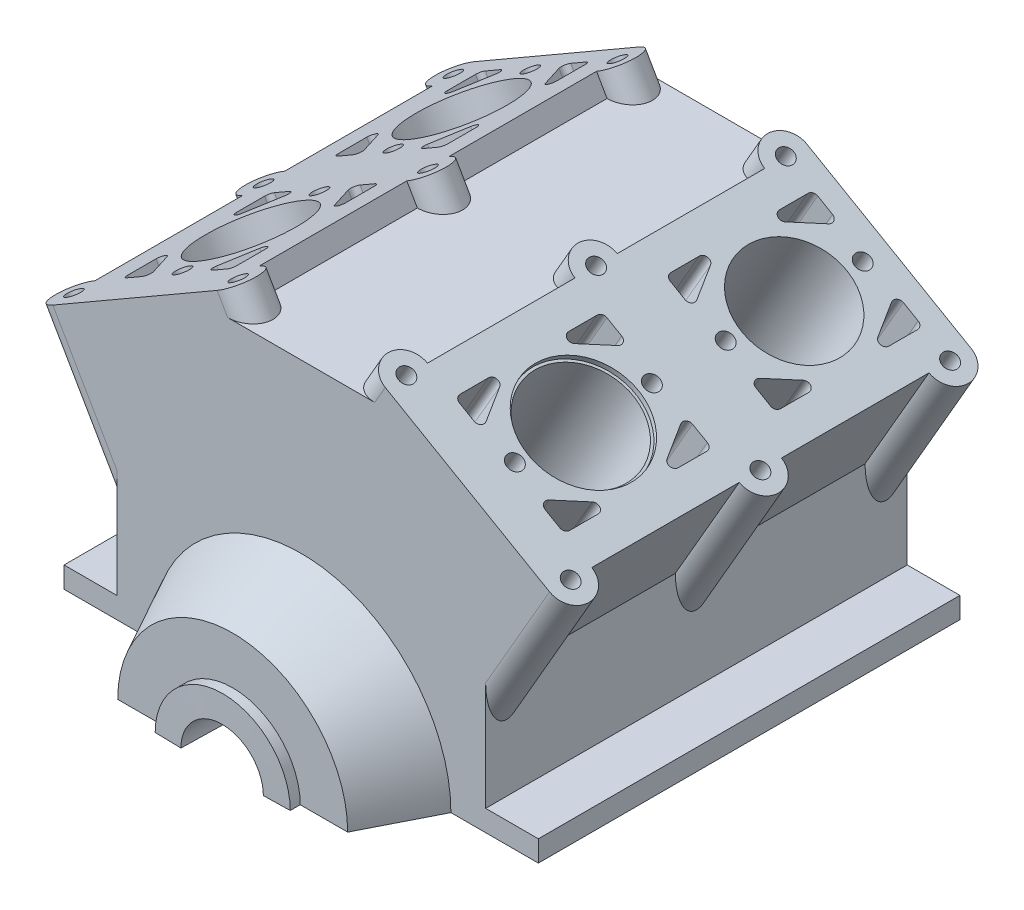
SolidWorks part; units mm, degrees
ref_plane "Front Plane" through (0, 0, 0) normal (0, 0, 1) x (1, 0, 0)
ref_plane "Top Plane" through (0, 0, 0) normal (0, 1, 0) x (1, 0, 0)
ref_plane "Right Plane" through (0, 0, 0) normal (1, 0, 0) x (0, 0, -1)
sketch "Sketch1" plane through (0, 0, 0) normal (0, 0, 1) x (1, 0, 0)
  line L0 (307.0364, 0) -> (-307.0364, 0) construction
  line L1 (0, 0) -> (0, 350) construction
  line L2 (0, 0) -> (0, 100) construction
  line L3 (-299.4563, 100) -> (299.4563, 100) construction
  line L4 (0, 0) -> (204.6694, 354.4979) construction
  line L5 (0, 0) -> (-204.6694, 354.4979) construction
  line L6 (37.5, 0) -> (225, 0)
  line L7 (225, 0) -> (225, 20)
  line L8 (225, 20) -> (175, 20)
  line L9 (175, 20) -> (175, 123.1089)
  line L10 (175, 123.1089) -> (235.6773, 228.2051)
  line L11 (235.6773, 228.2051) -> (79.7927, 318.2051)
  line L12 (79.7927, 318.2051) -> (69.7927, 300.8846)
  line L13 (69.7927, 300.8846) -> (-69.7927, 300.8846)
  line L14 (-37.5, 0) -> (-225, 0)
  line L15 (-225, 0) -> (-225, 20)
  line L16 (-225, 20) -> (-175, 20)
  line L17 (-175, 20) -> (-175, 123.1089)
  line L18 (-175, 123.1089) -> (-235.6773, 228.2051)
  line L19 (-235.6773, 228.2051) -> (-79.7927, 318.2051)
  line L20 (-79.7927, 318.2051) -> (-69.7927, 300.8846)
  arc A0 (-37.5, 0) -> (37.5, 0) centre (0, 0) cw
  point P18 (157.735, 273.2051)
  point P21 (57.735, 100)
  point P29 (0, 300.8846)
  dimension "D1" = 100
  dimension "D3" = 37.5
  dimension "D2" = 187.5
  dimension "D4" = 200
  dimension "D5" = 20
  dimension "D6" = 180
  dimension "D7" = 20
  dimension "D8" = 50
  dimension "D9" = 300.8846
extrude "Boss-Extrude1" add sketch "Sketch1" along normal blind 400
ref_plane "Plane4" through (0, 0, 380) normal (0, 0, 1) x (1, 0, 0)
sketch "Sketch2" plane through (0, 0, 380) normal (0, 0, 1) x (1, 0, 0)
  line L0 (-155, 0) -> (155, 0)
  arc A0 (-155, 0) -> (155, 0) centre (0, 0) cw
  dimension "D1" = 310
extrude "Cut-Extrude5" cut sketch "Sketch2" against normal offset from surface (360 mm away) 20 up to face at (0, 128.6442, 0)
sketch "Sketch4" plane through (157.735, 273.2051, 0) normal (0.5, 0.866, 0) x (0.866, -0.5, 0)
  line L0 (90, -400) -> (90, 0) construction
  line L1 (90, -400) -> (-90, -400) construction
  circle A0 centre (90, -380) radius 20
  dimension "D1" = 40
extrude "Head Bolt Holder" add sketch "Sketch4" against normal up to next
hole_wizard "Ø15.0 (15) Diameter Hole1" positions "3DSketch1" profile "Sketch8" hole size "Ø15.0" standard "ANSI Metric"
sketch3d "3DSketch1"
  point P0 (235.6773, 228.2051, 380)
sketch "Sketch8" plane through (235.6773, 228.2051, 380) normal (0, 0, 1) x (-0.866, 0.5, 0)
  line L0 (0, 0) -> (0, 119.5065)
  line L1 (0, 119.5065) -> (7.5, 115)
  line L2 (7.5, 115) -> (7.5, 0)
  line L5 (7.5, 0) -> (0, 0)
  line L10 (0, 119.5065) -> (-7.5, 115) construction
  line L11 (0, -6.35) -> (0, 107.95) construction
  dimension "Hole Dia." = 15
  dimension "Hole Depth" = 115
  dimension "Drill Angle" = 118
pattern_linear "LPattern4" count 3 spacing 180 along (0, 0, -1) of "Head Bolt Holder", "Ø15.0 (15) Diameter Hole1"
ref_axis "Axis1" through (0, 0, 420) along (0, 0, -1)
ref_plane "Plane9" through (0, 0, 0) normal (0.866, -0.5, 0) x (0, 0, -1)
mirror "Mirror3" about plane through (0, 0, 0) normal (0.866, -0.5, 0) of "LPattern4"
mirror "Mirror4" about plane through (0, 0, 0) normal (1, 0, 0) of "LPattern4", "Mirror3"
sketch "Sketch11" plane through (157.735, 273.2051, 0) normal (0.5, 0.866, 0) x (0.866, -0.5, 0)
  line L0 (0, -400) -> (0, -290) construction
  line L1 (90, -400) -> (-90, -400) construction
  line L2 (0, -242) -> (0, 242) construction
  line L3 (-60, -400) -> (-60, -360) construction
  line L4 (60, -328.0516) -> (60, -355)
  line L5 (-55, -360) -> (-38.831, -360)
  line L6 (-34.5435, -352.4275) -> (-50.7125, -325.4791)
  line L7 (-60, -328.0516) -> (-60, -355)
  line L8 (34.5435, -352.4275) -> (50.7125, -325.4791)
  line L9 (55, -360) -> (38.831, -360)
  line L10 (-73.0995, -290) -> (90, -290) construction
  line L11 (-175.0128, -380) -> (175.0128, -380) construction
  line L12 (-60, -251.9484) -> (-60, -225)
  line L13 (-34.5435, -227.5725) -> (-50.7125, -254.5209)
  line L14 (-55, -220) -> (-38.831, -220)
  line L15 (34.5435, -227.5725) -> (50.7125, -254.5209)
  line L16 (55, -220) -> (38.831, -220)
  line L17 (60, -251.9484) -> (60, -225)
  circle A0 centre (0, -290) radius 50
  circle A1 centre (0, -290) radius 52.5
  arc A2 (-34.5435, -352.4275) -> (-38.831, -360) centre (-38.831, -355) cw
  arc A3 (-60, -328.0516) -> (-50.7125, -325.4791) centre (-55, -328.0516) cw
  arc A4 (-60, -355) -> (-55, -360) centre (-55, -355) ccw
  arc A5 (60, -328.0516) -> (50.7125, -325.4791) centre (55, -328.0516) ccw
  arc A6 (34.5435, -352.4275) -> (38.831, -360) centre (38.831, -355) ccw
  arc A7 (60, -355) -> (55, -360) centre (55, -355) cw
  circle A8 centre (0, -355) radius 7.5
  arc A9 (-60, -251.9484) -> (-50.7125, -254.5209) centre (-55, -251.9484) ccw
  arc A10 (-34.5435, -227.5725) -> (-38.831, -220) centre (-38.831, -225) ccw
  arc A11 (-60, -225) -> (-55, -220) centre (-55, -225) cw
  circle A12 centre (0, -225) radius 7.5
  arc A13 (60, -251.9484) -> (50.7125, -254.5209) centre (55, -251.9484) cw
  arc A14 (34.5435, -227.5725) -> (38.831, -220) centre (38.831, -225) cw
  arc A15 (60, -225) -> (55, -220) centre (55, -225) ccw
  point P16 (-30, -360)
  point P19 (-60, -310)
  dimension "D1" = 50
  dimension "D3" = 100
  dimension "D4" = 105
  dimension "D6" = 5
  dimension "D2" = 30
  dimension "D5" = 110
extrude "Cut-Extrude6" cut sketch "Sketch11" against normal through all contours A0
extrude "Cut-Extrude7" cut sketch "Sketch11<3>" against normal blind 115 contours A11 L12 A9 L13 A10 L14 | L17 A15 L16 A14 L15 A13 | A7 L4 A5 L8 A6 L9 | L7 A4 L5 A2 L6 A3 | A12 | A8 region at (200.8043, 248.339, 344.8882) region at (114.6658, 298.0711, 344.8882) region at (114.6658, 298.0711, 235.1118) region at (200.8043, 248.339, 235.1118)
sketch "Sketch11<3>" plane through (157.735, 273.2051, 0) normal (0.5, 0.866, 0) x (0.866, -0.5, 0) same geometry as "Sketch11"
extrude "Cut-Extrude8" cut sketch "Sketch11<4>" against normal blind 5 contours A1 A0 region at (113.5547, 298.7126, 290)
sketch "Sketch11<4>" plane through (157.735, 273.2051, 0) normal (0.5, 0.866, 0) x (0.866, -0.5, 0) same geometry as "Sketch11"
sketch "Sketch12" plane through (0, 0, 0) normal (0, 0, 1) x (1, 0, 0)
  line L0 (69.7927, 300.8846) -> (-69.7927, 300.8846) construction
  line L2 (0, 300.8846) -> (0, 0) construction
  circle A0 centre (0, 250.8846) radius 20
  circle A1 centre (0, 250.8846) radius 27.5
  point P4 (0, 300.8846)
  dimension "D1" = 50
  dimension "D3" = 55
extrude "Boss-Extrude2" add sketch "Sketch12" against normal blind 20
pattern_linear "LPattern6" count 2 spacing 200 along (0, 0, -1) of "Cut-Extrude6", "Cut-Extrude7"
mirror "Mirror6" about plane through (0, 0, 0) normal (1, 0, 0) of "LPattern6"
sketch "Sketch13" plane through (0, 0, 0) normal (0, 1, 0) x (1, 0, 0)
  line L0 (37.5, -400) -> (39.0861, -475)
  line L1 (39.0861, -475) -> (64.0861, -474.4713)
  line L2 (64.0861, -474.4713) -> (64.0861, -465)
  line L3 (64.0861, -465) -> (109.0861, -465)
  line L4 (109.0861, -465) -> (142.0304, -400)
  line L6 (235.6773, -400) -> (79.7927, -400) construction
  line L7 (38.3578, 75) -> (38.3578, 0)
  line L8 (38.3578, 75) -> (63.3578, 75)
  line L9 (63.3578, 75) -> (63.3578, 65)
  line L10 (63.3578, 65) -> (108.3578, 65)
  line L11 (108.3578, 65) -> (142.0304, 0)
  line L12 (235.6773, 0) -> (79.7927, 0) construction
  line L13 (37.5, 0) -> (225, 0) construction
  line L14 (37.5, -400) -> (142.0304, -400)
  line L15 (38.3578, 0) -> (142.0304, 0)
  point P10 (157.735, 0)
  dimension "D1" = 75
  dimension "D2" = 45
  dimension "D3" = 25
  dimension "D4" = 65
  dimension "D5" = 75
  dimension "D6" = 25
  dimension "D7" = 45
  dimension "D8" = 65
revolve "Revolve2" add sketch "Sketch13" angle 180 about axis through (0, 0, 420) along (0, 0, -1) reverse direction yes
